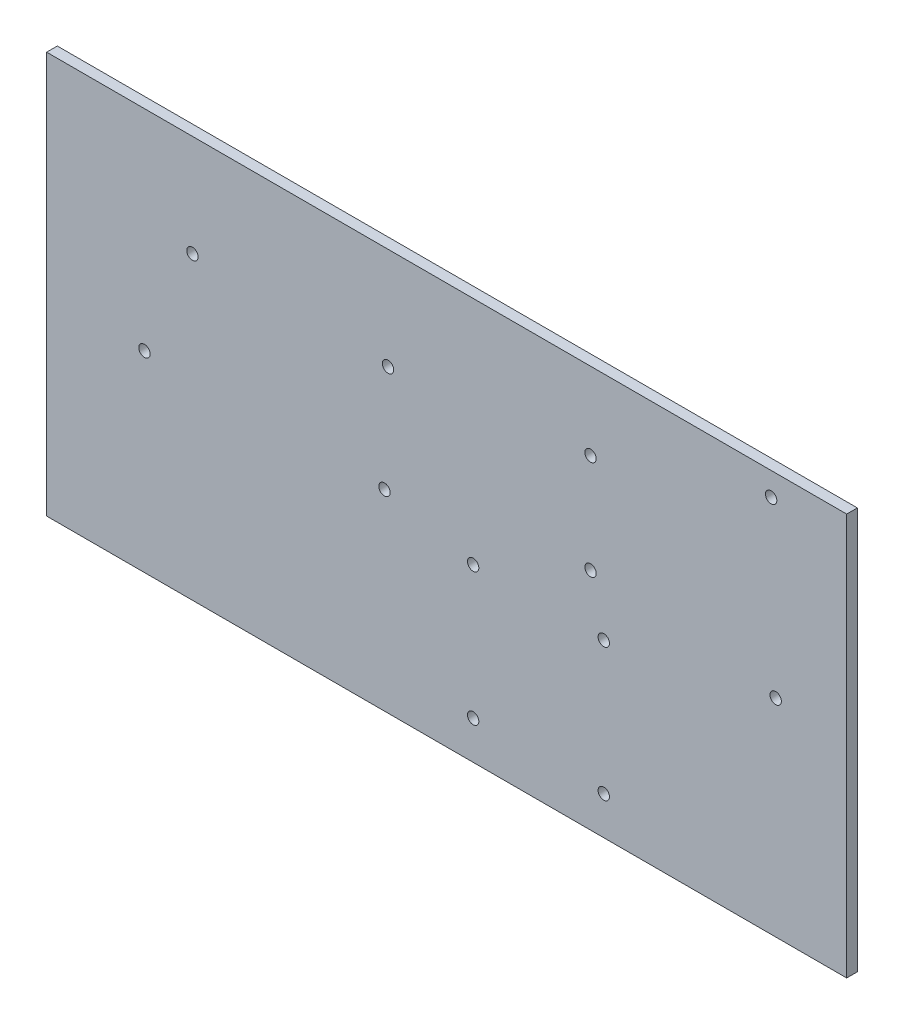
SolidWorks part; units mm, degrees
material "Сосна"
ref_plane "Спереди" through (0, 0, 0) normal (0, 0, 1) x (1, 0, 0)
ref_plane "Сверху" through (0, 0, 0) normal (0, 1, 0) x (1, 0, 0)
ref_plane "Справа" through (0, 0, 0) normal (1, 0, 0) x (0, 0, -1)
sketch "Эскиз1" plane through (0, 0, 0) normal (0, 0, 1) x (1, 0, 0)
  line L4 (112.5, -56.5) -> (112.5, 56.5)
  line L5 (112.5, 56.5) -> (-112.5, 56.5)
  line L6 (-112.5, 56.5) -> (-112.5, -56.5)
  line L7 (-112.5, -56.5) -> (112.5, -56.5)
  line L8 (112.5, -56.5) -> (112.5, 56.5)
  line L9 (112.5, 56.5) -> (-112.5, 56.5)
  line L10 (-112.5, 56.5) -> (-112.5, -56.5)
  line L11 (-112.5, -56.5) -> (112.5, -56.5)
  dimension "D1" = 0
extrude "Бобышка-Вытянуть1" add sketch "Эскиз1" along normal blind 3 contours L11 L8 L9 L10
hole_wizard "Отверстие с зазором M31" positions "Эскиз4" profile "Эскиз5" hole size "M3" standard "ISO" end condition up to next
sketch "Эскиз4" plane through (0, 0, 0) normal (0, 0, -1) x (-1, 0, 0)
  point P0 (-92.53, 1.7)
  point P3 (-40.46, 6.78)
  point P6 (-40.46, 34.72)
  point P9 (-91.26, 49.96)
  point P12 (-44.1857, -8.3637)
  point P15 (-7.4439, -8.3637)
  point P18 (-7.4439, -45.7432)
  point P21 (-44.1857, -45.7432)
  point P24 (17.5, -2.5)
  point P27 (85, -2.5)
  point P30 (71.5, 27.9)
  point P33 (16.5, 27.9)
sketch "Эскиз5" plane through (92.53, 1.7, 0) normal (1, 0, 0) x (0, 1, 0)
  line L0 (0, 0) -> (0, 3)
  line L1 (0, 3) -> (1.6, 3)
  line L2 (1.6, 3) -> (1.6, 0)
  line L5 (1.6, 0) -> (0, 0)
  line L11 (0, -6.35) -> (0, 107.95) construction
  dimension "Диаметр сквозного отверстия" = 3.2
  dimension "Глубина сквозного отверстия" = 3
